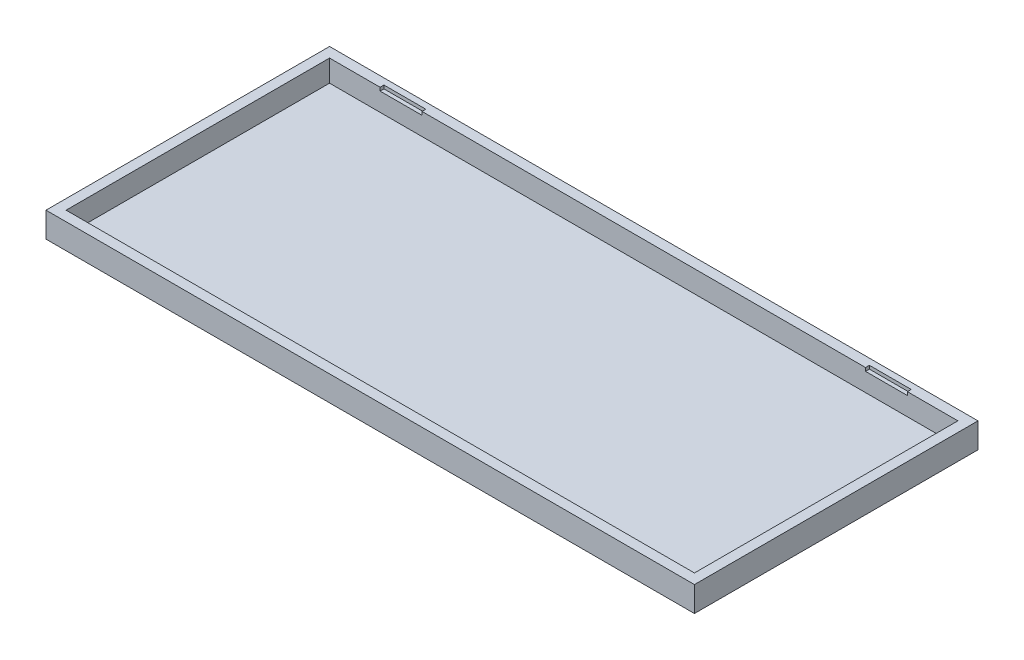
SolidWorks part; units mm, degrees
ref_plane "Front Plane" through (0, 0, 0) normal (0, 0, 1) x (1, 0, 0)
ref_plane "Top Plane" through (0, 0, 0) normal (0, 1, 0) x (1, 0, 0)
ref_plane "Right Plane" through (0, 0, 0) normal (1, 0, 0) x (0, 0, -1)
sketch "Sketch1" plane through (0, 0, 0) normal (0, 1, 0) x (1, 0, 0)
  line L1 (-193.7, 84.7) -> (193.7, 84.7)
  line L2 (-193.7, 84.7) -> (-193.7, -84.7)
  line L3 (-193.7, -84.7) -> (193.7, -84.7)
  line L4 (193.7, 84.7) -> (193.7, -84.7)
  line L5 (-193.7, 84.7) -> (193.7, -84.7) construction
  line L6 (-193.7, -84.7) -> (193.7, 84.7) construction
  point P0 (0, 0)
  dimension "D1" = 387.4
  dimension "D2" = 169.4
extrude "Boss-Extrude1" add sketch "Sketch1" along normal blind 15
sketch "Sketch2" plane through (0, 15, 0) normal (0, 1, 0) x (1, 0, 0)
  line L0 (0, 78.7) -> (0, 84.7) construction
  line L2 (-187.7, 78.7) -> (187.7, 78.7)
  line L3 (-187.7, 78.7) -> (-187.7, -78.7)
  line L4 (-187.7, -78.7) -> (187.7, -78.7)
  line L5 (187.7, 78.7) -> (187.7, -78.7)
  line L6 (-187.7, 78.7) -> (187.7, -78.7) construction
  line L7 (-187.7, -78.7) -> (187.7, 78.7) construction
  line L8 (193.7, 84.7) -> (-193.7, 84.7) construction
  line L9 (187.7, 0) -> (193.7, 0) construction
  line L10 (193.7, -84.7) -> (193.7, 84.7) construction
  point P0 (0, 0)
  dimension "D1" = 6
  dimension "D2" = 6
extrude "Cut-Extrude1" cut sketch "Sketch2" against normal offset from surface (13 mm away) 2 up to face at (0, 0, 0)
sketch "Sketch3" plane through (0, 15, 0) normal (0, 1, 0) x (1, 0, 0)
  line L0 (193.7, 84.7) -> (157.5, 84.7) construction
  line L1 (193.7, 84.7) -> (-193.7, 84.7) construction
  line L2 (157.5, 81) -> (157.5, 78.7)
  line L3 (-187.7, 78.7) -> (187.7, 78.7) construction
  line L4 (157.5, 78.7) -> (132.5, 78.7)
  line L5 (187.7, 78.7) -> (-187.7, 78.7) construction
  line L6 (132.5, 78.7) -> (132.5, 81)
  line L7 (132.5, 81) -> (157.5, 81)
  line L8 (157.5, 81) -> (157.5, 84.7) construction
  line L9 (-193.7, 84.7) -> (-157.5, 84.7) construction
  line L10 (-157.5, 81) -> (-157.5, 78.7)
  line L11 (-157.5, 78.7) -> (-132.5, 78.7)
  line L12 (-132.5, 78.7) -> (-132.5, 81)
  line L13 (-132.5, 81) -> (-157.5, 81)
  line L14 (-157.5, 81) -> (-157.5, 84.7) construction
  dimension "D1" = 36.2
  dimension "D2" = 2.3
  dimension "D3" = 25
  dimension "D4" = 36.2
  dimension "D5" = 2.3
  dimension "D6" = 25
extrude "Cut-Extrude2" cut sketch "Sketch3" against normal blind 2
equation "\"full_width\"=375"
equation "\"D1@Sketch1\"=\"full_width\"+(\"added_width\"*2)+(\"margin1\"*2)"
equation "\"added_width\" =6"
equation "\"full_height\"= 157"
equation "\"D2@Sketch1\"=\"full_height\"+(\"added_height\"*2)+(\"margin1\"*2)"
equation "\"added_height\"=6"
equation "\"D1@Sketch3\"=30.00mm+\"added_width\"+\"margin1\""
equation "\"tab_depth\"=2.5"
equation "\"D2@Sketch3\"=\"tab_depth\"-\"margin1\""
equation "\"tab_width\"=25"
equation "\"D3@Sketch3\"=\"tab_width\""
equation "\"tab_height\"=2"
equation "\"D1@Cut-Extrude2\"=\"tab_height\""
equation "\"D4@Sketch3\"=30mm+\"added_width\"+\"margin1\""
equation "\"D5@Sketch3\"=\"tab_depth\"-\"margin1\""
equation "\"D6@Sketch3\"=\"tab_width\""
equation "\"D2@Sketch2\"=\"added_height\""
equation "\"D1@Sketch2\"=\"added_width\""
equation "\"margin1\"= 0.2"
